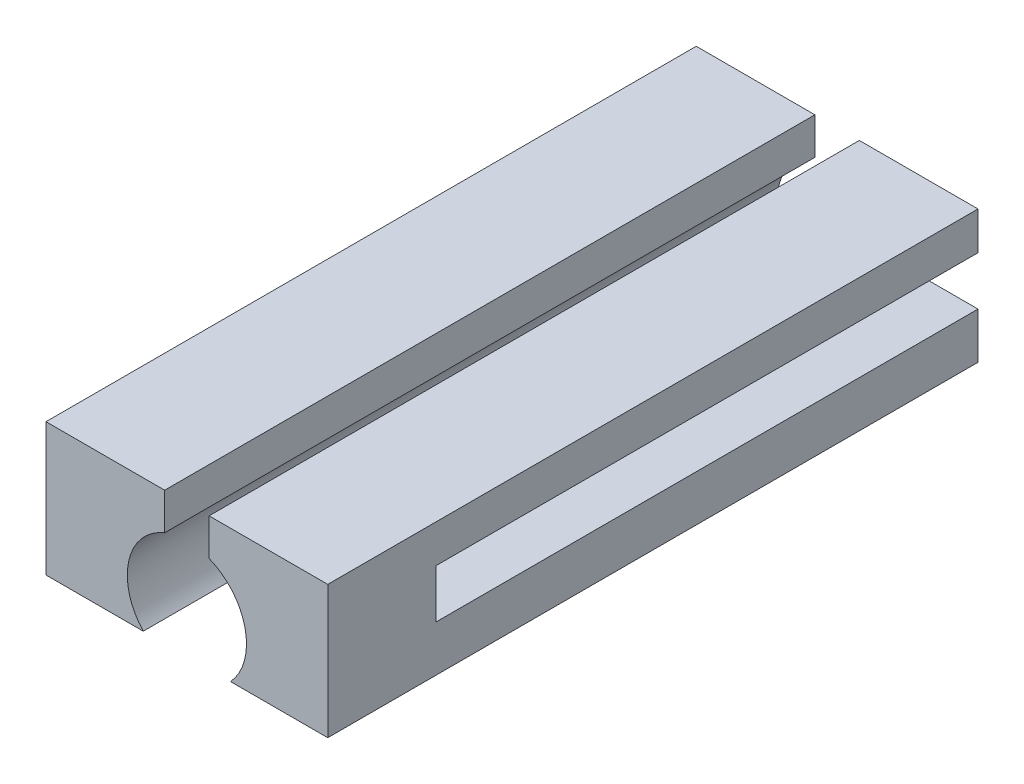
SolidWorks part; units mm, degrees
ref_plane "정면" through (0, 0, 0) normal (0, 0, 1) x (1, 0, 0)
ref_plane "윗면" through (0, 0, 0) normal (0, 1, 0) x (1, 0, 0)
ref_plane "우측면" through (0, 0, 0) normal (1, 0, 0) x (0, 0, -1)
sketch "스케치1" plane through (0, 0, 0) normal (0, 0, 1) x (1, 0, 0)
  line L0 (0, 17.5) -> (0, -17.5) construction
  line L1 (26, -17.5) -> (-26, -17.5)
  line L2 (-26, -17.5) -> (-26, 4)
  line L3 (-26, 4) -> (-9.5197, 14.6842)
  line L4 (-26, -7.5) -> (26, -7.5)
  line L6 (26, -17.5) -> (26, 4)
  line L7 (26, 4) -> (9.5197, 14.6842)
  line L8 (-4.1, 17.0129) -> (-4.1, 10.2074)
  line L9 (4.1, 17.0129) -> (4.1, 10.2074)
  circle A0 centre (0, 0) radius 17.5
  circle A1 centre (0, 0) radius 11
  dimension "D1" = 22
  dimension "D2" = 6.5
  dimension "D3" = 10
  dimension "D4" = 8.2
  dimension "D5" = 4
  dimension "D6" = 52
extrude "보스-돌출1" add sketch "스케치1" along normal mid plane 120 contours A0 L3 L2 L4 | A1 L8 A0 L4 region at (-11.6573, 4.4955, 0) region at (-20.7768, 0.4494, 0)
sketch "스케치2" plane through (0, 0, 0) normal (0, 1, 0) x (1, 0, 0)
  line L0 (-26, 60) -> (-26, 70)
  line L1 (-26, 70) -> (-16, 60)
  line L2 (-26, 60) -> (-9.5197, 60) construction
  line L3 (-16, 60) -> (-26, 60)
  dimension "D1" = 45
  dimension "D2" = 10
extrude "보스-돌출2" add sketch "스케치2" against normal up to vertex (7.5 mm away) and the other way blind 11 up to point (-8.0467, -7.5, -60)
sketch "스케치3" plane through (0, 0, 0) normal (0, 0, 1) x (1, 0, 0)
  line L0 (-26, 4) -> (-15.2025, 11)
  line L1 (-26, 4) -> (-9.5197, 14.6842) construction
  line L2 (-15.2025, 11) -> (-26, 11)
  line L3 (-26, 11) -> (-26, 4)
extrude "컷-돌출1" cut sketch "스케치3" against normal through all both and the other way through all
mirror "대칭 복사5" about plane through (0, 0, 0) normal (1, 0, 0) of bodies 103
sketch "스케치4" plane through (0, 0, 0) normal (0, 1, 0) x (1, 0, 0)
  line L0 (-16, 60) -> (-26, 60)
  line L1 (-26, -60) -> (-26, 70) construction
  line L2 (-26, 60) -> (-26, 72.4)
  line L3 (-26, 72.4) -> (27.7861, 72.4)
  line L4 (27.7861, 72.4) -> (27.7861, 60)
  line L5 (27.7861, 60) -> (-26, 60)
extrude "컷-돌출2" cut sketch "스케치4" against normal blind 32 and the other way blind 36 contours L2 L3 L4 L5
ref_plane "평면1" through (0, 0, 60) normal (0, 0, 1) x (1, 0, 0)
sketch "스케치5" plane through (0, 0, 60) normal (0, 0, 1) x (1, 0, 0)
  line L0 (-26, 4) -> (-26, 17.0129)
  line L1 (-26, 17.0129) -> (-4.1, 17.0129)
  line L2 (-4.1, 17.0129) -> (-6.9087, 16.0786)
  line L3 (-6.9087, 16.0786) -> (-26, 4)
  line L4 (26, 4) -> (26, 17.0129)
  line L5 (26, 17.0129) -> (4.1, 17.0129)
  line L6 (4.1, 17.0129) -> (6.9087, 16.0786)
  line L7 (6.9087, 16.0786) -> (26, 4)
  arc A0 (-4.1, 17.0129) -> (-9.5197, 14.6842) centre (0, 0) ccw construction
  arc A1 (9.5197, 14.6842) -> (4.1, 17.0129) centre (0, 0) ccw construction
  point P0 (-4.1, 17.0129)
  point P1 (4.1, 17.0129)
extrude "보스-돌출3" add sketch "스케치5" against normal up to vertex (120 mm away) contours L6 L7 L4 L5 | L1 L2 L3 L0 region at (19.0807, 12.6939, 60) up to point (-26, 4, -60)
sketch "스케치8" plane through (26, 0, 0) normal (1, 0, 0) x (0, 0, -1)
  line L0 (60, 1.0129) -> (-40, 1.0129)
  line L1 (60, 17.0129) -> (60, -7.5) construction
  line L2 (-40, 1.0129) -> (-40, 10.0129)
  line L3 (-40, 10.0129) -> (60, 10.0129)
  line L4 (60, 10.0129) -> (60, 1.0129)
  line L5 (60, 17.0129) -> (-60, 17.0129) construction
  dimension "D1" = 100
  dimension "D2" = 9
  dimension "D3" = 7
sketch "스케치9" plane through (0, 0, -60) normal (0, 0, -1) x (-1, 0, 0)
  line L0 (-26, 10.0129) -> (-16, 10.0129)
  line L1 (-26, 10.0129) -> (-26, 1.0129) construction
  line L2 (-26, 1.0129) -> (-26, 10.0129) construction
  line L3 (-16, 10.0129) -> (-16, 14.0129)
  line L4 (-16, 14.0129) -> (-12.5, 14.0129)
  line L5 (-12.5, 14.0129) -> (-12.5, -2.9871)
  line L6 (-12.5, -2.9871) -> (-16.3665, -2.9871)
  line L7 (-16.3665, -2.9871) -> (-16.3665, 1.0129)
  line L8 (-16.3665, 1.0129) -> (-26, 1.0129)
  line L9 (-26, 17.0129) -> (-26, -7.5) construction
  line L10 (-26, 1.0129) -> (-26, 10.0129)
  line M8 (-26, 17.0129) -> (-26, -7.5)
  dimension "D1" = 4
  dimension "D2" = 4
  dimension "D3" = 17
  dimension "D4" = 10
  dimension "D5" = 3.5
extrude "컷-돌출3" cut sketch "스케치9" against normal up to vertex (100 mm away) contours L8 L7 L6 L5 L4 L3 L0 M8 region at (18.2929, 5.4498, -60) up to point (26, 1.0129, 40)
